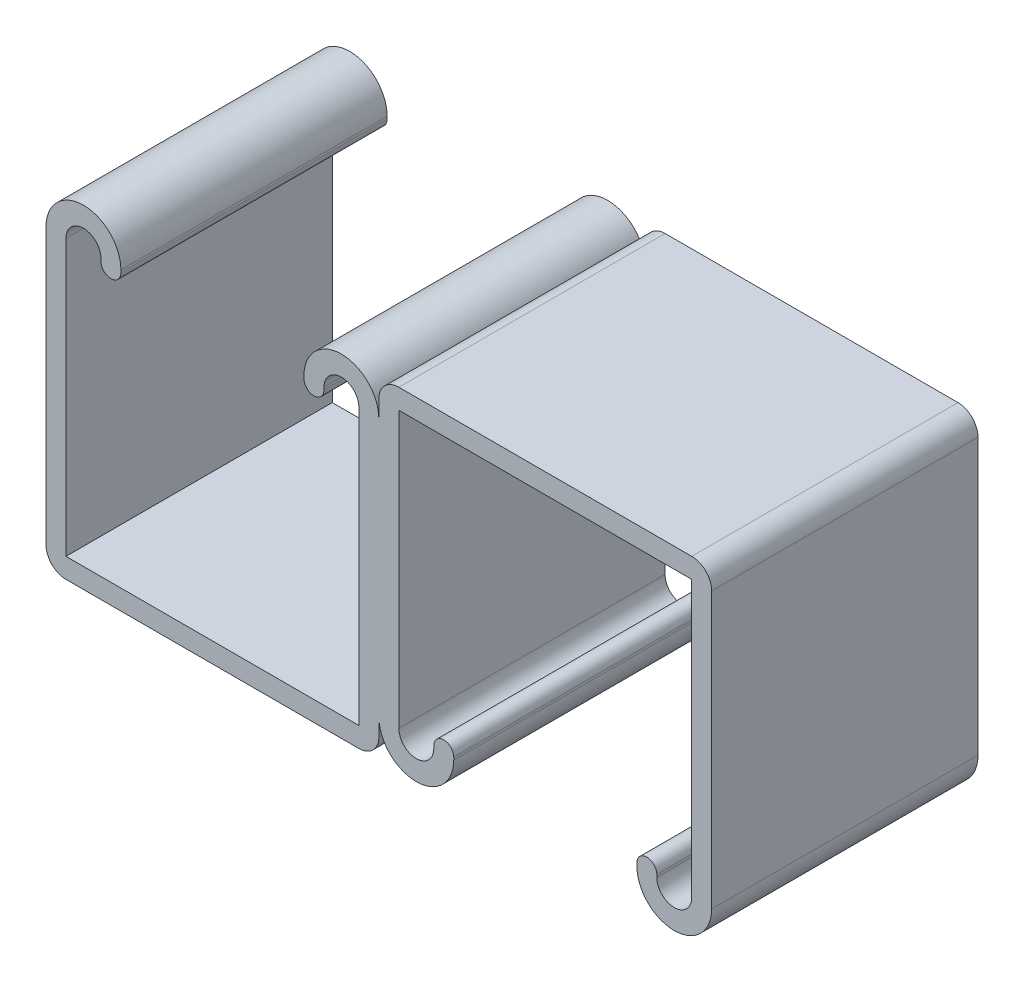
SolidWorks part; units mm, degrees
note: '?' marks a value the reader was unsure of.
ref_plane "Plane1" through (0, 0, 0) normal (0, 0, 1) x (1, 0, 0)
ref_plane "Plane2" through (0, 0, 0) normal (0, 1, 0) x (1, 0, 0)
ref_plane "Plane3" through (0, 0, 0) normal (1, 0, 0) x (0, 0, -1)
sketch "Sketch1" plane through (0, 0, 0) normal (0, 0, 1) x (1, 0, 0)
  line L0 (-31.75, 12.3031) -> (-31.75, -13.97)
  line L1 (-29.845, -15.875) -> (-1.905, -15.875)
  line L2 (0, -13.97) -> (0, 12.3031)
  line L3 (-7.1438, 12.3031) -> (-7.1438, 12.065)
  line L4 (-24.6062, 12.3031) -> (-24.6062, 12.065)
  line L5 (-26.5112, 12.3031) -> (-26.5113, 12.065)
  line L6 (-29.845, 12.3031) -> (-29.845, -13.97)
  line L7 (-29.845, -13.97) -> (-1.905, -13.97)
  line L8 (-1.905, -13.97) -> (-1.905, 12.3031)
  line L9 (-5.2388, 12.3031) -> (-5.2388, 12.065)
  line L10 (-44.483, 15.875) -> (25.4, 15.875) construction
  line L11 (-36.5125, 11.1125) -> (12.8524, 11.1125) construction
  arc A0 (0, 12.3031) -> (-7.1438, 12.3031) centre (-3.5719, 12.3031) ccw
  arc A1 (-31.75, 12.3031) -> (-24.6062, 12.3031) centre (-28.1781, 12.3031) cw
  arc A2 (-29.845, -15.875) -> (-31.75, -13.97) centre (-29.845, -13.97) cw
  arc A3 (-1.905, -15.875) -> (0, -13.97) centre (-1.905, -13.97) ccw
  arc A4 (-29.845, 12.3031) -> (-26.5112, 12.3031) centre (-28.1781, 12.3031) cw
  arc A5 (-1.905, 12.3031) -> (-5.2388, 12.3031) centre (-3.5719, 12.3031) ccw
  arc A6 (-7.1438, 12.065) -> (-5.2388, 12.065) centre (-6.1913, 12.065) ccw
  arc A7 (-24.6062, 12.065) -> (-26.5113, 12.065) centre (-25.5587, 12.065) cw
  dimension "D5" = 15.875
  dimension "D6" = 7.1437
  dimension "D7" = 17.4625
  dimension "D8" = 15.875
  dimension "D9" = 4.7625
extrude "Base-Extrude" add sketch "Sketch1" along normal mid plane 25.4
ref_axis "Axis1" through (0, 0, -50) along (0, 0, 1)?
pattern_circular "CirPattern1" count 2 every 180 about axis through (0, 0, 0) along (0, 0, 1) of "Base-Extrude"
equation "\"D7@Sketch1\" = \"Width@Sketch1\" - 2 * \"D6@Sketch1\""
equation "\"D1@Sketch1\" = \"gauge@Sketch1\""
